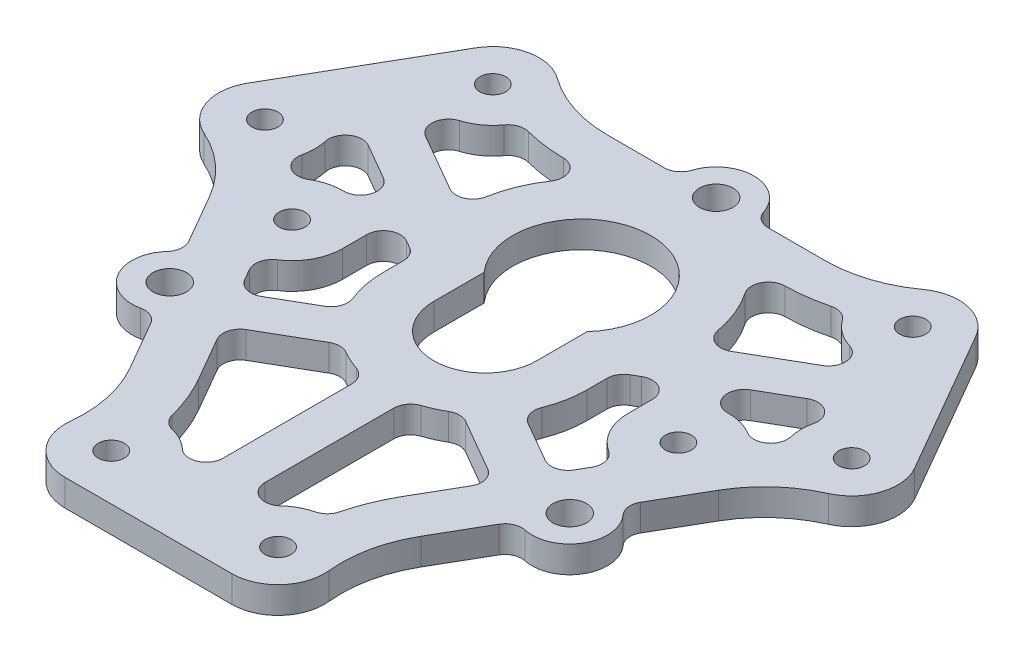
SolidWorks part; units mm, degrees
material "5052-H32"
ref_plane "Front Plane" through (0, 0, 0) normal (0, 0, 1) x (1, 0, 0)
ref_plane "Top Plane" through (0, 0, 0) normal (0, 1, 0) x (1, 0, 0)
ref_plane "Right Plane" through (0, 0, 0) normal (1, 0, 0) x (0, 0, -1)
sketch "Sketch1" plane through (0, 0, 0) normal (0, 1, 0) x (1, 0, 0)
  line L0 (0, 0) -> (0, 36) construction
  line L1 (-12.9662, 27.5) -> (12.9662, 27.5)
  line L2 (30.2988, -2.5209) -> (17.3326, -24.9791)
  line L3 (-25, 25.9037) -> (25, 25.9037) construction
  line L4 (-17.3326, -24.9791) -> (-30.2988, -2.5209)
  line L5 (29.7631, 28.6537) -> (39.6964, 11.4488)
  line L6 (9.9332, -40.1025) -> (-9.9332, -40.1025)
  line L7 (-29.7631, 28.6537) -> (-39.6964, 11.4488)
  line L8 (-6.125, 0) -> (-6.125, 6)
  line L9 (6.125, 0) -> (6.125, 6)
  circle A0 centre (0, 0) radius 6.125
  circle A1 centre (0, 0) radius 36 construction
  circle A2 centre (-25, 25.9037) radius 1.55
  circle A3 centre (25, 25.9037) radius 1.55
  arc A4 (-21.7714, 30.3563) -> (-29.7631, 28.6537) centre (-25, 25.9037) ccw
  arc A5 (29.7631, 28.6537) -> (21.7714, 30.3563) centre (25, 25.9037) ccw
  arc A6 (-21.7714, 30.3563) -> (-12.9662, 27.5) centre (-12.9662, 42.5) ccw
  arc A7 (12.9662, 27.5) -> (21.7714, 30.3563) centre (12.9662, 42.5) ccw
  arc A8 (37.1751, 3.6764) -> (39.6964, 11.4488) centre (34.9332, 8.6988) ccw
  circle A9 centre (34.9332, 8.6988) radius 1.55
  arc A10 (37.1751, 3.6764) -> (30.2988, -2.5209) centre (43.2892, -10.0209) ccw
  arc A11 (17.3326, -24.9791) -> (15.4037, -34.0328) centre (30.323, -32.4791) ccw
  arc A12 (9.9332, -40.1025) -> (15.4037, -34.0328) centre (9.9332, -34.6025) ccw
  arc A13 (-15.4037, -34.0328) -> (-9.9332, -40.1025) centre (-9.9332, -34.6025) ccw
  circle A14 centre (-9.9332, -34.6025) radius 1.55
  arc A15 (-15.4037, -34.0328) -> (-17.3326, -24.9791) centre (-30.323, -32.4791) ccw
  arc A16 (-30.2988, -2.5209) -> (-37.1751, 3.6764) centre (-43.2892, -10.0209) ccw
  arc A17 (-39.6964, 11.4488) -> (-37.1751, 3.6764) centre (-34.9332, 8.6988) ccw
  circle A18 centre (9.9332, -34.6025) radius 1.55
  circle A19 centre (-34.9332, 8.6988) radius 1.55
  arc A20 (6.125, 6) -> (-6.125, 6) centre (0, 11.4895) ccw
  circle A21 centre (0, 0) radius 8.225 construction
  circle A22 centre (-23, 0) radius 1.55
  circle A23 centre (23, 0) radius 1.55
  point P9 (0, 0)
  point P11 (0, 27.5)
  point P43 (0, 0)
  dimension "D1" = 12.25
  dimension "D2" = 72
  dimension "D4" = 3.1
  dimension "D5" = 11
  dimension "D6" = 15
  dimension "D9" = 16.45
  dimension "D3" = 50
  dimension "D8" = 27.5
  dimension "D10" = 6
  dimension "D11" = 23
  dimension "D7" = 3
extrude "Boss-Extrude1" add sketch "Sketch1" along normal blind 3.175 contours L7 A17 A16 L4 A15 A13 L6 A12 A11 L2 A10 A8 L5 A5 A7 L1 A6 A4 A20 L9 A0 L8 A19 A18 A2 A3 A9 A14 region at (0, 0, -26.4205)
sketch "Sketch6" plane through (0, 3.175, 0) normal (0, 1, 0) x (1, 0, 0)
  line L0 (-12.9662, 27.5) -> (12.9662, 27.5) construction
  line L1 (2, 27.5) -> (6.1847, 27.5)
  line L2 (22.8157, -15.4821) -> (20.7234, -19.1061)
  line L3 (-6.1847, 27.5) -> (-2, 27.5)
  line L4 (26.908, -8.3939) -> (24.8157, -12.0179)
  line L5 (-24.8157, -12.0179) -> (-26.908, -8.3939)
  line L6 (-20.7234, -19.1061) -> (-22.8157, -15.4821)
  circle A0 centre (0, 27.5) radius 2
  arc A1 (4.2817, 28.8846) -> (-4.2817, 28.8846) centre (0, 27.5) ccw
  arc A2 (-6.1847, 27.5) -> (-4.2817, 28.8846) centre (-6.1847, 29.5) ccw
  arc A3 (6.1847, 27.5) -> (4.2817, 28.8846) centre (6.1847, 29.5) cw
  arc A4 (20.7234, -19.1061) -> (22.874, -18.1504) centre (22.4554, -20.1061) cw
  arc A5 (22.874, -18.1504) -> (27.1557, -10.7343) centre (23.8157, -13.75) ccw
  arc A6 (26.908, -8.3939) -> (27.1557, -10.7343) centre (28.6401, -9.3939) ccw
  circle A7 centre (23.8157, -13.75) radius 2
  arc A8 (-26.908, -8.3939) -> (-27.1557, -10.7343) centre (-28.6401, -9.3939) cw
  arc A9 (-27.1557, -10.7343) -> (-22.874, -18.1504) centre (-23.8157, -13.75) ccw
  arc A10 (-20.7234, -19.1061) -> (-22.874, -18.1504) centre (-22.4554, -20.1061) ccw
  circle A11 centre (-23.8157, -13.75) radius 2
  point P35 (0, 0)
  line M4 (-30.2988, -2.5209) -> (-17.3326, -24.9791)
  line M10 (17.3326, -24.9791) -> (30.2988, -2.5209)
  line M16 (12.9662, 27.5) -> (-12.9662, 27.5)
  dimension "D1" = 4
  dimension "D2" = 9
  dimension "D3" = 2
  dimension "D4" = 3
extrude "Boss-Extrude2" add sketch "Sketch6" against normal up to surface (3.175 mm away) contours A3 A1 A2 A0 M16 | A11 A8 A9 A10 M4 | A7 A4 A5 A6 M10 region at (0, 3.175, -29.6006) region at (25.6348, 3.175, 14.8003) region at (-25.6348, 3.175, 14.8003) up to face at (0, 0, 0)
extrude "Cut-Extrude1" cut sketch "Sketch6<3>" against normal up to surface (3.175 mm away) contours A0 | A7 | A11 up to face at (0, 0, 0)
sketch "Sketch6<3>" plane through (0, 3.175, 0) normal (0, 1, 0) x (1, 0, 0) same geometry as "Sketch6"
sketch "Sketch8" plane through (0, 3.175, 0) normal (0, 1, 0) x (1, 0, 0)
  line L0 (-34.7298, 20.0512) -> (0, 0) construction
  line L1 (-29.7631, 28.6537) -> (-39.6964, 11.4488) construction
  line L2 (0, 0) -> (34.7298, 20.0512) construction
  line L3 (29.7631, 28.6537) -> (39.6964, 11.4488) construction
  line L4 (0, 0) -> (0, -40.1025) construction
  line L5 (9.9332, -40.1025) -> (-9.9332, -40.1025) construction
  line L6 (-23.6313, 16.5303) -> (-16.7528, 12.559)
  line L7 (0, 0) -> (0, 11.4895) construction
  line L8 (26.1313, 12.2002) -> (21.8541, 9.7307)
  line L9 (-14, 4.6188) -> (-13.125, 4.1136)
  line L10 (2.5, -13.389) -> (2.5, -28.7305)
  line L11 (9.9332, -34.1025) -> (-9.9332, -34.1025)
  line L12 (-0.0006, 2.8871) -> (0, 2.8868)
  line L13 (-33.4798, 22.2163) -> (1.25, 2.1651) construction
  line L14 (23.6313, 16.5303) -> (16.7528, 12.559)
  line L15 (-24.1608, -13.9492) -> (0, 0) construction
  line L16 (-17, 0) -> (-17, 2.8868)
  line L17 (-12.125, 0) -> (-12.125, 6)
  line L18 (-12.125, 0) -> (-12.125, 2.3816)
  line L19 (-19.6195, -9.0179) -> (-20.375, -7.7094)
  line L20 (9.9332, -34.1025) -> (0, -34.1025)
  line L21 (-16.8875, -9.75) -> (-12.1094, -6.9913)
  line L22 (12.1364, -21.9791) -> (15.1195, -16.8122)
  line L23 (-14.3875, -14.0801) -> (-8.1248, -10.4644)
  line L24 (14.3875, -14.0801) -> (8.1248, -10.4644)
  line L25 (12.125, 0) -> (12.125, 2.3816)
  line L26 (-12.1364, -21.9791) -> (-15.5272, -16.1061)
  line L27 (-12.1364, -21.9791) -> (-15.1195, -16.8122)
  line L28 (-36.2298, 17.4532) -> (-1.5, -2.5981) construction
  line L29 (-21.6608, -18.2794) -> (2.5, -4.3301) construction
  line L30 (-2.5, -13.389) -> (-2.5, -28.7305)
  line L31 (16.8875, -9.75) -> (12.1094, -6.9913)
  line L32 (19.6195, -9.0179) -> (20.375, -7.7094)
  line L33 (17, 0) -> (17, 2.8868)
  line L34 (14, 4.6188) -> (13.125, 4.1136)
  line L35 (-26.1313, 12.2002) -> (-21.8541, 9.7307)
  line L36 (-35.9798, 17.8862) -> (-1.25, -2.1651) construction
  circle A0 centre (-25, 25.9037) radius 1.55 construction
  arc A1 (-11.568, 19.375) -> (-13.7837, 13.9409) centre (0, 11.4895) ccw
  arc A2 (-16.7528, 12.559) -> (-13.7837, 13.9409) centre (-15.7528, 14.2911) ccw
  arc A3 (-11.568, 19.375) -> (-13.1975, 22.5013) centre (-13.2206, 20.5015) ccw
  arc A4 (-18.0149, 23.1477) -> (-20.1399, 22.3853) centre (-18.5198, 21.2125) ccw
  arc A5 (-23.6313, 16.5303) -> (-23.2235, 20.1727) centre (-22.6313, 18.2624) cw
  arc A6 (6.125, 6) -> (-6.125, 6) centre (0, 11.4895) ccw construction
  arc A7 (11.568, 19.375) -> (13.7837, 13.9409) centre (0, 11.4895) cw
  arc A8 (16.7528, 12.559) -> (13.7837, 13.9409) centre (15.7528, 14.2911) cw
  arc A9 (23.6313, 16.5303) -> (23.2235, 20.1727) centre (22.6313, 18.2624) ccw
  arc A10 (23.2235, 20.1727) -> (20.1399, 22.3853) centre (25, 25.9037) cw
  arc A11 (-23.2235, 20.1727) -> (-20.1399, 22.3853) centre (-25, 25.9037) ccw
  arc A12 (18.0149, 23.1477) -> (20.1399, 22.3853) centre (18.5198, 21.2125) cw
  arc A13 (-24.7065, 26.3085) -> (-12.9662, 22.5) centre (-12.9662, 42.5) ccw
  arc A14 (-18.0149, 23.1477) -> (-13.1975, 22.5013) centre (-12.9662, 42.5) ccw
  arc A15 (18.0149, 23.1477) -> (13.1975, 22.5013) centre (12.9662, 42.5) cw
  arc A16 (11.568, 19.375) -> (13.1975, 22.5013) centre (13.2206, 20.5015) cw
  arc A17 (-19.7322, -5.0321) -> (-17, 0) centre (-23, 0) ccw
  arc A18 (-6.116, -10.4695) -> (-3.8628, -11.4932) centre (0, 0) ccw
  arc A19 (-5.8583, -30.1985) -> (-8.5034, -28.7753) centre (-9.9332, -34.6025) ccw
  arc A20 (-8.5034, -28.7753) -> (-9.9656, -27.3239) centre (-8.0268, -26.833) cw
  arc A21 (-15.1195, -16.8122) -> (-14.3875, -14.0801) centre (-13.3875, -15.8122) cw
  arc A22 (-12.125, 0) -> (12.125, 0) centre (0, 0) ccw
  arc A23 (-12.125, 0) -> (-11.2532, -4.5146) centre (0, 0) ccw
  arc A24 (-8.1248, -10.4644) -> (-6.116, -10.4695) centre (-7.1248, -12.1964) cw
  arc A25 (-3.8628, -11.4932) -> (-2.5, -13.389) centre (-4.5, -13.389) cw
  arc A26 (-13.125, 4.1136) -> (-12.125, 2.3816) centre (-14.125, 2.3816) cw
  arc A27 (-9.4359, -34.6543) -> (-12.1364, -21.9791) centre (-30.323, -32.4791) ccw
  arc A28 (-9.9656, -27.3239) -> (-12.1364, -21.9791) centre (-30.323, -32.4791) ccw
  arc A29 (-11.2532, -4.5146) -> (-12.1094, -6.9913) centre (-13.1094, -5.2593) cw
  arc A30 (-16.8875, -9.75) -> (-19.6195, -9.0179) centre (-17.8875, -8.0179) cw
  arc A31 (-20.375, -7.7094) -> (-19.7322, -5.0321) centre (-18.643, -6.7094) cw
  arc A32 (-17, 2.8868) -> (-14, 4.6188) centre (-15, 2.8868) cw
  arc A33 (-5.8583, -30.1985) -> (-2.5, -28.7305) centre (-4.5, -28.7305) ccw
  arc A34 (5.8583, -30.1985) -> (2.5, -28.7305) centre (4.5, -28.7305) cw
  arc A35 (5.8583, -30.1985) -> (8.5034, -28.7753) centre (9.9332, -34.6025) cw
  arc A36 (8.5034, -28.7753) -> (9.9656, -27.3239) centre (8.0268, -26.833) ccw
  arc A37 (9.9656, -27.3239) -> (12.1364, -21.9791) centre (30.323, -32.4791) cw
  arc A38 (15.1195, -16.8122) -> (14.3875, -14.0801) centre (13.3875, -15.8122) ccw
  arc A39 (8.1248, -10.4644) -> (6.116, -10.4695) centre (7.1248, -12.1964) ccw
  arc A40 (6.116, -10.4695) -> (3.8628, -11.4932) centre (0, 0) cw
  arc A41 (3.8628, -11.4932) -> (2.5, -13.389) centre (4.5, -13.389) ccw
  arc A42 (12.125, 0) -> (11.2532, -4.5146) centre (0, 0) cw
  arc A43 (11.2532, -4.5146) -> (12.1094, -6.9913) centre (13.1094, -5.2593) ccw
  arc A44 (16.8875, -9.75) -> (19.6195, -9.0179) centre (17.8875, -8.0179) ccw
  arc A45 (20.375, -7.7094) -> (19.7322, -5.0321) centre (18.643, -6.7094) ccw
  arc A46 (19.7322, -5.0321) -> (17, 0) centre (23, 0) cw
  arc A47 (17, 2.8868) -> (14, 4.6188) centre (15, 2.8868) ccw
  arc A48 (13.125, 4.1136) -> (12.125, 2.3816) centre (14.125, 2.3816) ccw
  arc A49 (-29.0978, 7.303) -> (-29.0818, 10.0258) centre (-34.9332, 8.6988) ccw
  arc A50 (-22.8906, 5.999) -> (-26.1145, 5.1283) centre (-23, 0) ccw
  arc A51 (22.8906, 5.999) -> (26.1145, 5.1283) centre (23, 0) cw
  arc A52 (-22.8906, 5.999) -> (-21.8541, 9.7307) centre (-22.8541, 7.9987) ccw
  arc A53 (29.0978, 7.303) -> (26.1145, 5.1283) centre (27.1527, 6.8378) cw
  arc A54 (29.0978, 7.303) -> (29.0818, 10.0258) centre (34.9332, 8.6988) cw
  arc A55 (-26.1313, 12.2002) -> (-29.0818, 10.0258) centre (-27.1313, 10.4681) ccw
  arc A56 (-19.7322, -5.0321) -> (-17, 0) centre (-23, 0) ccw
  arc A57 (-29.0978, 7.303) -> (-26.1145, 5.1283) centre (-27.1527, 6.8378) ccw
  arc A58 (26.1313, 12.2002) -> (29.0818, 10.0258) centre (27.1313, 10.4681) cw
  arc A59 (22.8906, 5.999) -> (21.8541, 9.7307) centre (22.8541, 7.9987) cw
  point P16 (-23.8157, -13.75)
  point P43 (-7.637, 23.2231)
  point P90 (-7.0662, -9.8532)
  point P93 (-2.5, -11.8645)
  point P100 (-18.6195, -10.75)
  dimension "D3" = 2
  dimension "D5" = 14
  dimension "D6" = 6
  dimension "D8" = 6
  dimension "D13" = 2
  dimension "D14" = 4
  dimension "D17" = 4
  dimension "D11" = 6
  dimension "D12" = 2.5
  dimension "D1" = 2.5
  dimension "D2" = 3
  dimension "D4" = 5
  dimension "D7" = 6
  dimension "D9" = 5
  dimension "D10" = 6
  dimension "D16" = 2.5
extrude "Cut-Extrude2" cut sketch "Sketch8" against normal up to surface (3.175 mm away) contours A14 A4 A11 A5 L6 A2 A1 A3 | A49 A57 A50 A52 L35 A55 | A32 L16 A17 A31 L19 A30 L21 A29 A23 L18 A26 L9 | A19 A33 L30 A25 A18 A24 L23 A21 L27 A28 A20 | A40 A41 L10 A34 A35 A36 A37 L22 A38 L24 A39 | L34 A48 L25 A42 A43 L31 A44 L32 A45 A46 L33 A47 | A59 A51 A53 A54 A58 L8 | A16 A7 A8 L14 A9 A10 A12 A15 region at (-17.5167, 3.175, -18.2163) region at (25.5847, 3.175, -8.5058) region at (15.4131, 3.175, 3.1835) region at (7.5605, 3.175, 19.6832) region at (-7.5605, 3.175, 19.6832) region at (-15.4131, 3.175, 3.1835) region at (17.5167, 3.175, -18.2163) region at (-25.5847, 3.175, -8.5058) up to face at (0, 0, 0)
